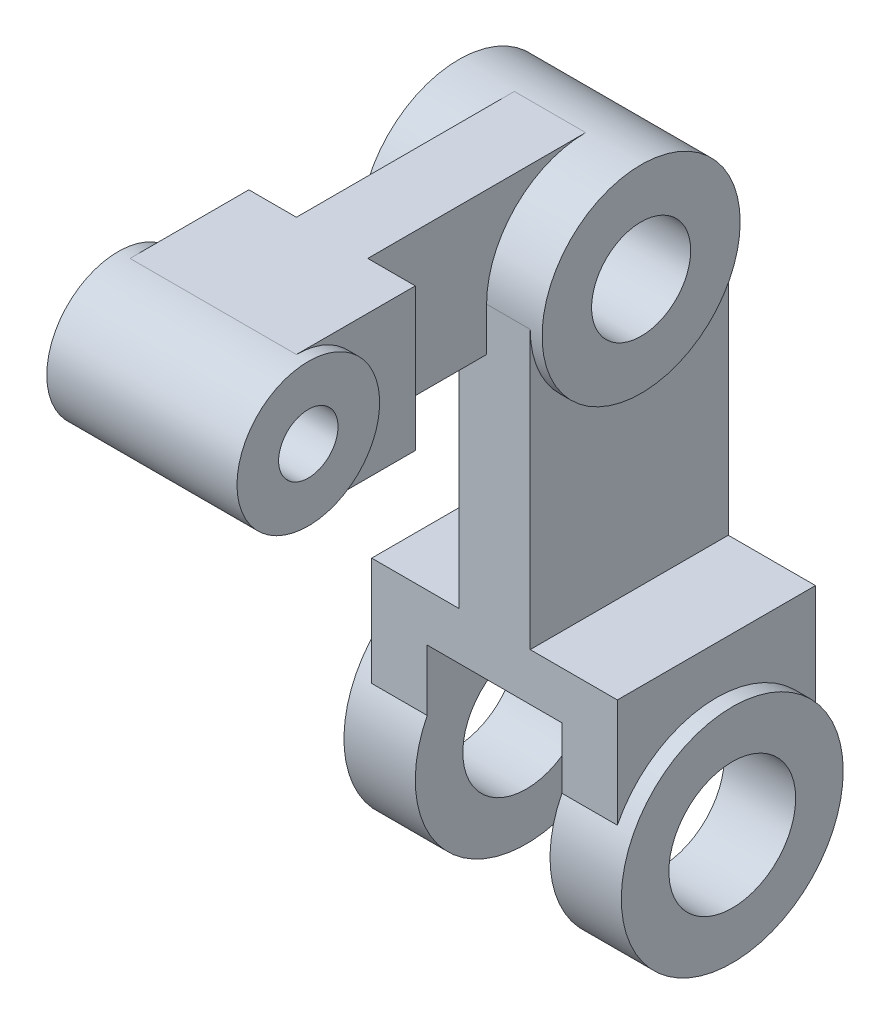
SolidWorks part; units mm, degrees
ref_plane "Front Plane" through (0, 0, 0) normal (0, 0, 1) x (1, 0, 0)
ref_plane "Top Plane" through (0, 0, 0) normal (0, 1, 0) x (1, 0, 0)
ref_plane "Right Plane" through (0, 0, 0) normal (1, 0, 0) x (0, 0, -1)
sketch "Sketch1" plane through (0, 0, 0) normal (1, 0, 0) x (0, 0, -1)
  circle A0 centre (0, 0) radius 16
  circle A1 centre (0, 0) radius 28
  dimension "D1" = 32
  dimension "D2" = 56
extrude "Boss-Extrude1" add sketch "Sketch1" along normal mid plane 70
sketch "Sketch2" plane through (0, 0, 0) normal (1, 0, 0) x (0, 0, -1)
  line L0 (-25, 40) -> (25, 40)
  line L1 (25, 40) -> (25, 12.6095)
  line L2 (-25, 40) -> (-25, 12.6095)
  line L3 (0, 40) -> (0, 0) construction
  circle A0 centre (0, 0) radius 28 construction
  circle A2 centre (0, 0) radius 28
  arc A3 (25, 12.6095) -> (-25, 12.6095) centre (0, 0) ccw
  point P3 (0, 40)
  dimension "D1" = 50
  dimension "D2" = 40
  dimension "D3" = 0
extrude "Boss-Extrude4" add sketch "Sketch2" along normal mid plane 62
sketch "Sketch6" plane through (0, 0, 0) normal (1, 0, 0) x (0, 0, -1)
  line L0 (-25, 40) -> (-25, 110)
  line L1 (25, 110) -> (25, 40)
  line L2 (-25, 40) -> (25, 40)
  circle A0 centre (0, 110) radius 12.5
  circle A1 centre (0, 110) radius 25
  dimension "D1" = 25
  dimension "D2" = 50
  dimension "D3" = 110
extrude "Boss-Extrude8" add sketch "Sketch6" along normal mid plane 18 contours A1 L0 L2 L1 region at (0, 65.4916, 0)
extrude "Boss-Extrude10" add sketch "Sketch6<8>" along normal blind 12 contours A1 A0 region at (0, 134.2929, 0)
sketch "Sketch6<8>" plane through (0, 0, 0) normal (1, 0, 0) x (0, 0, -1) same geometry as "Sketch6"
extrude "Boss-Extrude11" add sketch "Sketch6<9>" against normal blind 34 contours A1 A0 region at (0, 134.2929, 0)
sketch "Sketch6<9>" plane through (0, 0, 0) normal (1, 0, 0) x (0, 0, -1) same geometry as "Sketch6"
sketch "Sketch8" plane through (0, 0, 0) normal (0, 0, 1) x (1, 0, 0)
  line L0 (-35, -28) -> (35, -28) construction
  line L1 (-17, 28) -> (17, 28)
  line L2 (-17, 28) -> (-17, -28)
  line L3 (-17, -28) -> (17, -28)
  line L4 (17, 28) -> (17, -28)
  line L5 (-9, 40) -> (-31, 40) construction
  point P8 (-20, 40)
  point P10 (0, -28)
  dimension "D1" = 12
  dimension "D2" = 34
extrude "Cut-Extrude2" cut sketch "Sketch8" against normal through all both and the other way through all
sketch "Sketch9" plane through (0, 0, 0) normal (0, 0, 1) x (1, 0, 0)
  line L0 (12, 135) -> (-34, 135) construction
  line L1 (-20, 99) -> (-2, 99)
  line L2 (-20, 99) -> (-20, 135)
  line L3 (-20, 135) -> (-2, 135)
  line L4 (-2, 99) -> (-2, 135)
  dimension "D1" = 14
  dimension "D2" = 36
  dimension "D3" = 18
extrude "Boss-Extrude12" add sketch "Sketch9" along normal blind 55
sketch "Sketch12" plane through (0, 0, 0) normal (1, 0, 0) x (0, 0, -1)
  circle A0 centre (0, 110) radius 12.5 construction
  circle A1 centre (0, 110) radius 12.5
extrude "Cut-Extrude3" cut sketch "Sketch12" against normal through all both
sketch "Sketch13" plane through (0, 0, 0) normal (0, 0, 1) x (1, 0, 0)
  line L4 (-20, 135) -> (-20, 99)
  line L5 (-20, 99) -> (-2, 99)
  line L6 (-2, 99) -> (-2, 135)
  line L7 (-2, 135) -> (-20, 135)
  line L8 (-20, 135) -> (-20, 99)
  line L9 (-20, 99) -> (-2, 99)
  line L10 (-2, 99) -> (-2, 135)
  line L11 (-2, 135) -> (-20, 135)
  dimension "D1" = 0
sketch "Sketch15" plane through (0, 0, 0) normal (0, 0, 1) x (1, 0, 0)
  line L4 (-20, 135) -> (-20, 99)
  line L5 (-20, 99) -> (-2, 99)
  line L6 (-2, 99) -> (-2, 135)
  line L7 (-2, 135) -> (-20, 135)
  line L8 (-20, 135) -> (-20, 99)
  line L9 (-20, 99) -> (-2, 99)
  line L10 (-2, 99) -> (-2, 135)
  line L11 (-2, 135) -> (-20, 135)
  dimension "D1" = 0
ref_plane "Plane1" through (0, 0, 55) normal (0, 0, 1) x (1, 0, 0)
sketch "Sketch18" plane through (0, 0, 55) normal (0, 0, 1) x (1, 0, 0)
  line L0 (-32, 135) -> (10, 135)
  line L1 (-2, 135) -> (-20, 135) construction
  line L2 (12, 135) -> (-2, 135) construction
  line L3 (-32, 99) -> (10, 99)
  line L4 (-20, 99) -> (-2, 99) construction
  line L5 (10, 99) -> (10, 135)
  line L6 (-11, 140.1491) -> (-11, 90.7351) construction
  line L7 (-32, 99) -> (-32, 135)
  point P13 (-11, 99)
  point P14 (-11, 135)
  dimension "D1" = 42
extrude "Boss-Extrude15" add sketch "Sketch18" along normal blind 30
sketch "Sketch25" plane through (0, 0, 55) normal (0, 0, 1) x (1, 0, 0)
  line L0 (-11, 135) -> (-11, 99) construction
  line L1 (-2, 135) -> (-20, 135) construction
  line L2 (-20, 99) -> (-2, 99) construction
ref_plane "Plane2" through (-11, 0, 0) normal (-1, 0, 0) x (0, 0, 1)
sketch "Sketch30" plane through (-11, 0, 0) normal (-1, 0, 0) x (0, 0, 1)
  line L0 (85, 135) -> (85, 99) construction
  circle A1 centre (85, 117) radius 7.5
  dimension "D2" = 15
extrude "Cut-Extrude8" cut sketch "Sketch30" against normal through all both and the other way through all
sketch "Sketch31" plane through (-11, 0, 0) normal (-1, 0, 0) x (0, 0, 1)
  line L0 (85, 124.5) -> (85, 109.5) construction
  circle A0 centre (85, 117) radius 18
  dimension "D1" = 36
extrude "Boss-Extrude18" add sketch "Sketch31" along normal mid plane 48
extrude "Cut-Extrude9" cut sketch "Sketch30<2>" against normal through all both and the other way through all
sketch "Sketch30<2>" plane through (-11, 0, 0) normal (-1, 0, 0) x (0, 0, 1) same geometry as "Sketch30"
